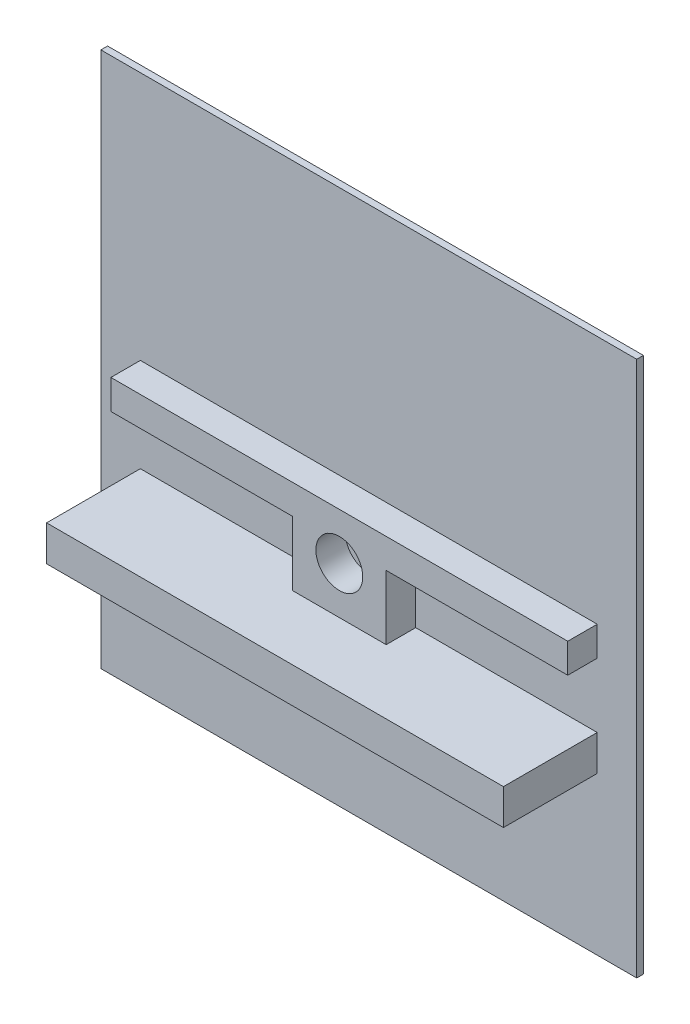
SolidWorks part; units mm, degrees
ref_plane "Plan de face" through (0, 0, 0) normal (0, 0, 1) x (1, 0, 0)
ref_plane "Plan de dessus" through (0, 0, 0) normal (0, 1, 0) x (1, 0, 0)
ref_plane "Plan de droite" through (0, 0, 0) normal (1, 0, 0) x (0, 0, -1)
sketch "Esquisse1" plane through (0, 0, 0) normal (0, 0, 1) x (1, 0, 0)
  line L1 (0, 0) -> (400, 0)
  line L2 (0, 0) -> (0, 400)
  line L3 (0, 400) -> (400, 400)
  line L4 (400, 0) -> (400, 400)
  dimension "D1" = 400
  dimension "D2" = 400
extrude "Boss.-Extru.1" add sketch "Esquisse1" against normal blind 5
sketch "Esquisse2" plane through (0, 0, 0) normal (0, 0, 1) x (1, 0, 0)
  line L0 (200, 400) -> (200, 0) construction
  line L1 (400, 400) -> (0, 400) construction
  line L2 (0, 0) -> (400, 0) construction
  line L3 (29.483, 213.9828) -> (29.483, 191.9828)
  line L4 (29.483, 191.9828) -> (165, 191.9828)
  line L5 (165, 191.9828) -> (165, 143.9828)
  line L6 (235, 191.9828) -> (235, 143.9828)
  line L7 (370.517, 191.9828) -> (235, 191.9828)
  line L8 (370.517, 213.9828) -> (370.517, 191.9828)
  line L9 (29.483, 213.9828) -> (370.517, 213.9828)
  line L10 (165, 143.9828) -> (235, 143.9828)
  circle A0 centre (200, 178.9828) radius 17.5
  dimension "D5" = 35
  dimension "D1" = 48
  dimension "D2" = 22
  dimension "D3" = 70
  dimension "D4" = 35
extrude "Boss.-Extru.2" add sketch "Esquisse2" along normal blind 22
sketch "Esquisse3" plane through (0, 0, 0) normal (0, 0, 1) x (1, 0, 0)
  line L0 (29.483, 143.9828) -> (370.517, 143.9828)
  line L1 (370.517, 143.9828) -> (370.517, 117.5002)
  line L2 (370.517, 117.5002) -> (29.483, 117.5002)
  line L3 (29.483, 117.5002) -> (29.483, 143.9828)
extrude "Boss.-Extru.3" add sketch "Esquisse3" along normal blind 70
